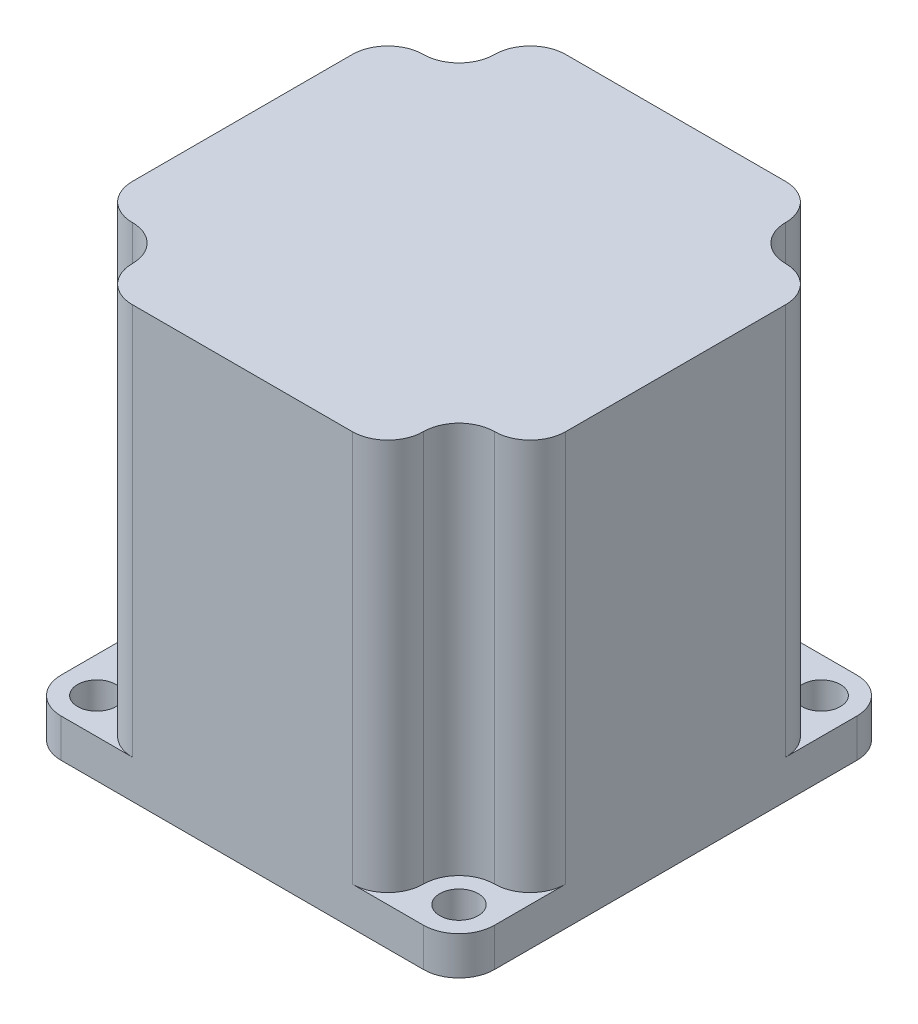
SolidWorks part; units mm, degrees
ref_plane "Front Plane" through (0, 0, 0) normal (0, 0, 1) x (1, 0, 0)
ref_plane "Top Plane" through (0, 0, 0) normal (0, 1, 0) x (1, 0, 0)
ref_plane "Right Plane" through (0, 0, 0) normal (1, 0, 0) x (0, 0, -1)
sketch "Sketch1" plane through (0, 0, 0) normal (0, 1, 0) x (1, 0, 0)
  line L1 (28.2, -28.2) -> (28.2, 28.2)
  line L2 (28.2, 28.2) -> (-28.2, 28.2)
  line L3 (-28.2, 28.2) -> (-28.2, -28.2)
  line L4 (-28.2, -28.2) -> (28.2, -28.2)
  circle A0 centre (0, 0) radius 28.2 construction
  point P1 (-23.57, 23.57)
  point P9 (0, 28.2)
  point P10 (-28.2, 0)
  point P12 (0, 0)
  point P14 (23.57, 23.57)
  point P15 (23.57, -23.57)
  point P16 (-23.57, -23.57)
  point P17 (0, 0)
  dimension "D1" = 56.4
  dimension "D2" = 23.57
  dimension "D3" = 23.57
  dimension "D5" = 6.5478
  dimension "D6" = 4.63
  dimension "D4" = 4
sketch "Sketch2" plane through (0, 0, 0) normal (0, 1, 0) x (1, 0, 0)
  circle A0 centre (0, 0) radius 19.05
extrude "Boss-Extrude1" add sketch "Sketch1" along normal blind 56
extrude "Boss-Extrude2" add sketch "Sketch2" against normal blind 1.6
sketch "Sketch3" plane through (0, -1.6, 0) normal (0, -1, 0) x (1, 0, 0)
  circle A0 centre (0, 0) radius 3.175
extrude "Boss-Extrude3" add sketch "Sketch3" along normal blind 19.4
sketch "Sketch4" plane through (0, -21, 0) normal (0, -1, 0) x (1, 0, 0)
  line L0 (-1.7861, 2.625) -> (1.7861, 2.625)
  arc A0 (1.7861, 2.625) -> (-1.7861, 2.625) centre (0, 0) ccw
  point P5 (0, -3.175)
  dimension "D1" = 5.8
extrude "Cut-Extrude1" cut sketch "Sketch4" against normal blind 16
hole_wizard "Ø5.0 (5) Diameter Hole1" positions "Sketch7" profile "Sketch6" hole size "Ø5.0" standard "ANSI Metric" end condition through all
sketch "Sketch7" plane through (0, 0, 0) normal (0, -1, 0) x (-1, 0, 0)
  point P0 (-23.57, 23.57)
  point P3 (23.57, 23.57)
  point P6 (23.57, -23.57)
  point P9 (-23.57, -23.57)
sketch "Sketch6" plane through (23.57, 0, -23.57) normal (1, 0, 0) x (0, 0, -1)
  line L0 (0, 0) -> (0, 56)
  line L1 (0, 56) -> (2.5, 56)
  line L2 (2.5, 56) -> (2.5, 0)
  line L5 (2.5, 0) -> (0, 0)
  line L11 (0, -6.35) -> (0, 107.95) construction
  dimension "Thru Hole Dia." = 5
  dimension "Thru Hole Depth" = 56
sketch "Sketch8" plane through (0, 56, 0) normal (0, 1, 0) x (1, 0, 0)
  line L1 (18.94, 18.94) -> (-18.94, 18.94) construction
  line L2 (-18.94, 18.94) -> (-18.94, -18.94) construction
  line L3 (-18.94, -18.94) -> (18.94, -18.94) construction
  line L4 (18.94, -18.94) -> (18.94, 18.94) construction
  line L5 (-28.2, 28.2) -> (-18.94, 28.2)
  line L6 (-28.2, 28.2) -> (-28.2, 18.94)
  line L7 (-28.2, 18.94) -> (-18.94, 18.94)
  line L8 (-18.94, 28.2) -> (-18.94, 18.94)
  line L9 (18.94, 18.94) -> (28.2, 18.94)
  line L10 (18.94, 18.94) -> (18.94, 28.2)
  line L11 (18.94, 28.2) -> (28.2, 28.2)
  line L12 (28.2, 18.94) -> (28.2, 28.2)
  line L13 (18.94, -18.94) -> (28.2, -18.94)
  line L14 (18.94, -18.94) -> (18.94, -28.2)
  line L15 (18.94, -28.2) -> (28.2, -28.2)
  line L16 (28.2, -18.94) -> (28.2, -28.2)
  line L17 (-28.2, -28.2) -> (-18.94, -28.2)
  line L18 (-28.2, -28.2) -> (-28.2, -18.94)
  line L19 (-28.2, -18.94) -> (-18.94, -18.94)
  line L20 (-18.94, -28.2) -> (-18.94, -18.94)
  dimension "D1" = 37.88
extrude "Cut-Extrude2" cut sketch "Sketch8" against normal offset from surface (51 mm away) 5 up to face at (23.57, 0, -26.07)
fillet "Fillet1" radius 4.63 16 edges at (28.2, 2.5, 28.2) (28.2, 2.5, -28.2) (18.94, 30.5, -28.2) (28.2, 30.5, -18.94) (18.94, 30.5, -18.94) (18.94, 30.5, 18.94) (18.94, 30.5, 28.2) (28.2, 30.5, 18.94) (-18.94, 30.5, 18.94) (-18.94, 30.5, 28.2) (-28.2, 2.5, 28.2) (-28.2, 30.5, 18.94) (-18.94, 30.5, -28.2) (-28.2, 30.5, -18.94) (-28.2, 2.5, -28.2) (-18.94, 30.5, -18.94)
